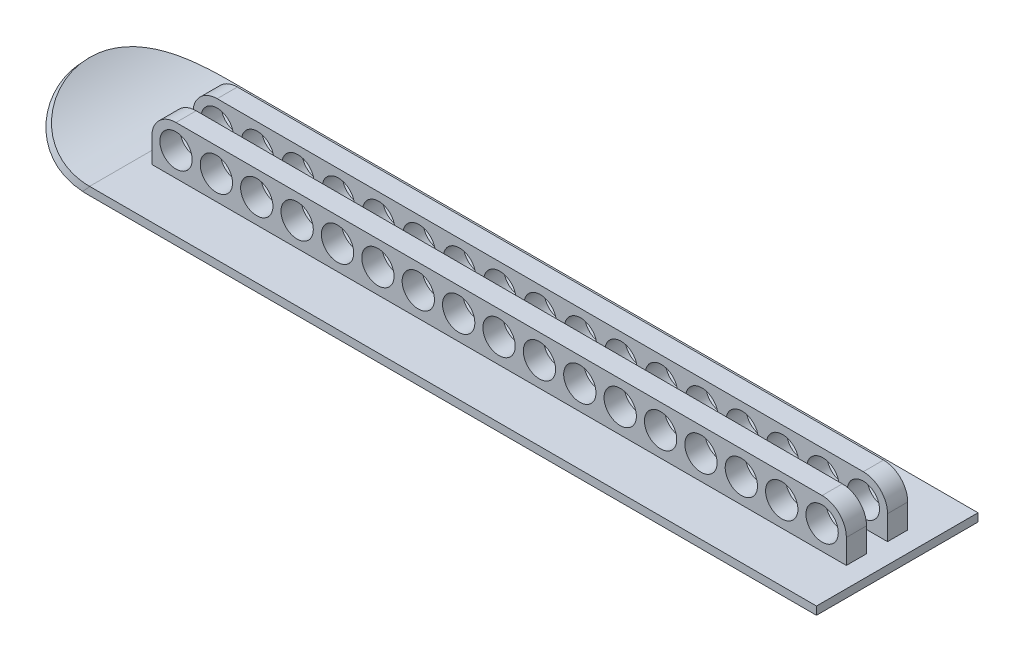
SolidWorks part; units mm, degrees
ref_plane "Front Plane" through (0, 0, 0) normal (0, 0, 1) x (1, 0, 0)
ref_plane "Top Plane" through (0, 0, 0) normal (0, 1, 0) x (1, 0, 0)
ref_plane "Right Plane" through (0, 0, 0) normal (1, 0, 0) x (0, 0, -1)
sketch "Sketch1" plane through (0, 0, 0) normal (0, 0, 1) x (1, 0, 0)
  line L0 (-255.7077, 10.3909) -> (-254, 12.2711)
  line L1 (0, 0) -> (-228.6, 0)
  line L2 (0, 0) -> (0, 2.54)
  line L3 (0, 2.54) -> (-228.6, 2.54)
  line L4 (-228.6, 0) -> (-228.6, 2.54)
  arc A0 (-255.7077, 10.3909) -> (-228.6, 0) centre (-228.6, 40.5548) ccw
  arc A1 (-254, 12.2711) -> (-228.6, 2.54) centre (-228.6, 40.5548) ccw
  dimension "D3" = 2.54
  dimension "D4" = 25.4
  dimension "D1" = 2.54
  dimension "D2" = 228.6
extrude "Boss-Extrude1" add sketch "Sketch1" along normal blind 50.8 contours L4 L1 L2 L3 | A1 L0 A0 L4 region at (-242.351, 4.6721, 0) region at (-114.3, 1.27, 0)
fillet "Fillet1" radius 25.4 2 edges at (-254.8539, 11.331, 0) (-254.8539, 11.331, 50.8)
sketch "Sketch2" plane through (0, 2.54, 0) normal (0, 1, 0) x (1, 0, 0)
  line L0 (0, -50.8) -> (0, 0) construction
  line L1 (-6.35, -15.748) -> (-224.79, -15.748)
  line L2 (-6.35, -15.748) -> (-6.35, -22.098)
  line L3 (-6.35, -22.098) -> (-224.79, -22.098)
  line L4 (-224.79, -15.748) -> (-224.79, -22.098)
  line L5 (-6.35, -28.702) -> (-224.79, -28.702)
  line L6 (-6.35, -28.702) -> (-6.35, -35.052)
  line L7 (-6.35, -35.052) -> (-224.79, -35.052)
  line L8 (-224.79, -28.702) -> (-224.79, -35.052)
  point P10 (0, -25.4)
  dimension "D1" = 6.604
  dimension "D2" = 6.35
  dimension "D3" = 6.35
  dimension "D4" = 3.302
  dimension "D5" = 6.35
  dimension "D6" = 218.44
extrude "Boss-Extrude2" add sketch "Sketch2" along normal blind 15.24
sketch "Sketch3" plane through (0, 0, 35.052) normal (0, 0, 1) x (1, 0, 0)
  line L0 (-6.35, 17.78) -> (-6.35, 2.54) construction
  line L1 (-224.79, 17.78) -> (-6.35, 17.78) construction
  line L2 (-13.97, 10.16) -> (-26.67, 10.16) construction
  circle A0 centre (-13.97, 10.16) radius 5.08
  circle A14 centre (-26.67, 10.16) radius 5.08
  circle A15 centre (-39.37, 10.16) radius 5.08
  circle A16 centre (-52.07, 10.16) radius 5.08
  circle A17 centre (-64.77, 10.16) radius 5.08
  circle A18 centre (-77.47, 10.16) radius 5.08
  circle A19 centre (-90.17, 10.16) radius 5.08
  circle A20 centre (-102.87, 10.16) radius 5.08
  circle A21 centre (-115.57, 10.16) radius 5.08
  circle A22 centre (-128.27, 10.16) radius 5.08
  circle A23 centre (-140.97, 10.16) radius 5.08
  circle A24 centre (-153.67, 10.16) radius 5.08
  circle A25 centre (-166.37, 10.16) radius 5.08
  circle A26 centre (-179.07, 10.16) radius 5.08
  circle A27 centre (-191.77, 10.16) radius 5.08
  circle A28 centre (-204.47, 10.16) radius 5.08
  circle A29 centre (-217.17, 10.16) radius 5.08
  dimension "D1" = 10.16
  dimension "D2" = 7.62
  dimension "D3" = 7.62
  dimension "D4" = 12.7
extrude "Cut-Extrude1" cut sketch "Sketch3" against normal through all
fillet "Fillet2" radius 7.62 4 edges at (-224.79, 17.78, 18.923) (-224.79, 17.78, 31.877) (-6.35, 17.78, 18.923) (-6.35, 17.78, 31.877)
